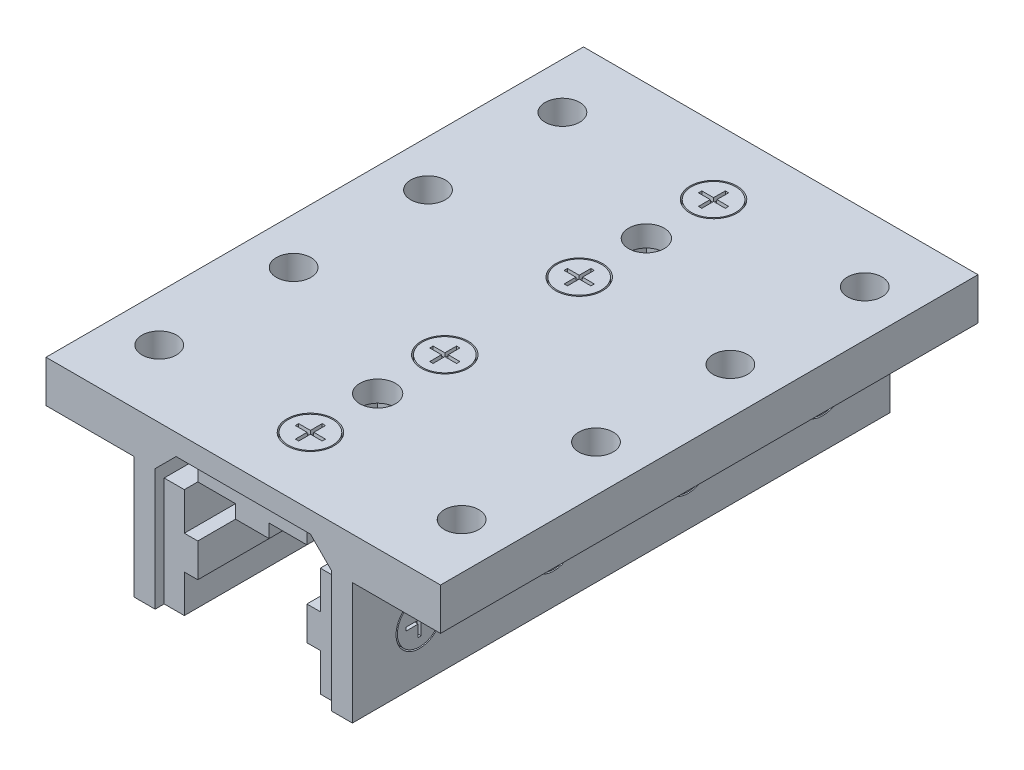
SolidWorks part; units mm, degrees
ref_plane "Front" through (0, 0, 0) normal (0, 0, 1) x (1, 0, 0)
ref_plane "Top" through (0, 0, 0) normal (0, 1, 0) x (1, 0, 0)
ref_plane "Right" through (0, 0, 0) normal (1, 0, 0) x (0, 0, -1)
sketch "Sketch1" plane through (0, 0, 0) normal (0, 0, 1) x (1, 0, 0)
  line L0 (-16.6624, 0) -> (-16.6624, 23.0124)
  line L1 (-20.6248, 30.9372) -> (20.6248, 30.9372)
  line L2 (-20.6248, 30.9372) -> (-20.6248, 0)
  line L3 (-20.6248, 0) -> (-16.6624, 0)
  line L4 (20.6248, 30.9372) -> (20.6248, 0)
  line L5 (-16.6624, 23.0124) -> (-12.7, 26.9748)
  line L6 (-12.7, 26.9748) -> (12.7, 26.9748)
  line L7 (12.7, 26.9748) -> (16.6624, 23.0124)
  line L8 (16.6624, 23.0124) -> (16.6624, 0)
  line L9 (16.6624, 0) -> (20.6248, 0)
  line L11 (-16.6624, 0) -> (16.6624, 0) construction
  dimension "D2" = 45
extrude "Boss-Extrude1" add sketch "Sketch1" along normal mid plane 50.8
sketch "Sketch2" plane through (0, 0, 0) normal (0, 0, 1) x (1, 0, 0)
  line L0 (-12.8524, 13.4874) -> (-12.8524, 20.6248)
  line L1 (-16.6624, 0) -> (-12.8524, 0)
  line L2 (-16.6624, 0) -> (-16.6624, 20.6248)
  line L3 (-16.6624, 20.6248) -> (-12.8524, 20.6248)
  line L4 (-12.8524, 0) -> (-12.8524, 7.1374)
  line L5 (-12.8524, 13.4874) -> (-10.3124, 13.4874)
  line L7 (-12.8524, 7.1374) -> (-10.3124, 7.1374)
  line L8 (-10.3124, 13.4874) -> (-10.3124, 7.1374)
  line L12 (-12.7, 26.9748) -> (12.7, 26.9748) construction
  line L13 (-10.3124, 26.9748) -> (10.3124, 26.9748)
  line L14 (-10.3124, 26.9748) -> (-10.3124, 23.1648)
  line L15 (-10.3124, 23.1648) -> (-3.175, 23.1648)
  line L16 (10.3124, 26.9748) -> (10.3124, 23.1648)
  line L17 (3.175, 23.1648) -> (10.3124, 23.1648)
  line L19 (-3.175, 23.1648) -> (-3.175, 20.6248)
  line L20 (-3.175, 20.6248) -> (3.175, 20.6248)
  line L21 (3.175, 23.1648) -> (3.175, 20.6248)
  point P14 (-10.3124, 10.3124)
  point P28 (0, 26.9748)
  dimension "Pad Wd" = 20.6248
  dimension "Pad Thick 1" = 6.35
  dimension "Pad Thick 2" = 3.81
  dimension "Pad Nose" = 6.35
extrude "Boss-Extrude2" add sketch "Sketch2" along normal mid plane 47.371 separate body
sketch "Sketch11" plane through (-10.3124, 0, 0) normal (1, 0, 0) x (0, 0, -1)
  line L0 (-23.6855, 13.4874) -> (23.6855, 13.4874) construction
  line L1 (-3.175, 13.4874) -> (3.175, 13.4874)
  line L2 (-3.175, 13.4874) -> (-3.175, 7.1374)
  line L3 (-3.175, 7.1374) -> (3.175, 7.1374)
  line L4 (3.175, 13.4874) -> (3.175, 7.1374)
  line L5 (-23.6855, 7.1374) -> (23.6855, 7.1374) construction
  point P8 (0, 13.4874)
extrude "Cut-Extrude5" cut sketch "Sketch11" against normal through all
sketch "Sketch12" plane through (0, 20.6248, 0) normal (0, -1, 0) x (1, 0, 0)
  line L0 (-3.175, 23.6855) -> (-3.175, -23.6855) construction
  line L1 (-3.175, 3.175) -> (3.175, 3.175)
  line L2 (-3.175, 3.175) -> (-3.175, -3.175)
  line L3 (-3.175, -3.175) -> (3.175, -3.175)
  line L4 (3.175, 3.175) -> (3.175, -3.175)
  line L5 (3.175, 23.6855) -> (3.175, -23.6855) construction
  point P8 (-3.175, 0)
extrude "Cut-Extrude6" cut sketch "Sketch12" against normal through all
mirror "Mirror1" about plane through (0, 0, 0) normal (1, 0, 0) of bodies 126 109
sketch "Sketch3" plane through (0, 30.9372, 0) normal (0, 1, 0) x (1, 0, 0)
  line L0 (0, -12.7) -> (0, 12.7) construction
  circle A0 centre (0, -12.7) radius 4.445
  circle A1 centre (0, -12.7) radius 4.191
extrude "Cut-Extrude1" cut sketch "Sketch3" against normal blind 1.9812
sketch "Sketch5" plane through (0, 30.9372, 0) normal (0, 1, 0) x (1, 0, 0)
  line L0 (0.3175, -12.3825) -> (2.54, -12.3825)
  line L1 (-0.3175, -10.16) -> (0.3175, -10.16)
  line L2 (-0.3175, -10.16) -> (-0.3175, -12.3825)
  line L3 (-0.3175, -15.24) -> (0.3175, -15.24)
  line L4 (0.3175, -10.16) -> (0.3175, -12.3825)
  line L5 (-2.54, -12.3825) -> (-0.3175, -12.3825)
  line L6 (-2.54, -12.3825) -> (-2.54, -13.0175)
  line L7 (-2.54, -13.0175) -> (-0.3175, -13.0175)
  line L8 (2.54, -12.3825) -> (2.54, -13.0175)
  line L9 (-0.3175, -13.0175) -> (-0.3175, -15.24)
  line L10 (0.3175, -13.0175) -> (0.3175, -15.24)
  line L11 (0.3175, -13.0175) -> (2.54, -13.0175)
  line L12 (-0.3175, -12.3825) -> (0.3175, -13.0175) construction
  dimension "D1" = 0.635
  dimension "D2" = 5.08
extrude "Cut-Extrude2" cut sketch "Sketch5" against normal blind 0.762 draft 5
sketch "Sketch13" plane through (20.6248, 0, 0) normal (1, 0, 0) x (0, 0, -1)
  circle A0 centre (-12.7, 10.3124) radius 4.445
  dimension "D1" = 8.89
extrude "Cut-Extrude-Thin1" cut sketch "Sketch13" against normal blind 1.9812 thin thin type one direction reverse wall 0.254
sketch "Sketch14" plane through (20.6248, 0, 0) normal (1, 0, 0) x (0, 0, -1)
  line L0 (-13.0175, 9.9949) -> (-13.0175, 7.7724)
  line L1 (-13.0175, 12.8524) -> (-12.3825, 12.8524)
  line L2 (-13.0175, 12.8524) -> (-13.0175, 10.6299)
  line L3 (-13.0175, 7.7724) -> (-12.3825, 7.7724)
  line L4 (-12.3825, 12.8524) -> (-12.3825, 10.6299)
  line L5 (-15.24, 10.6299) -> (-13.0175, 10.6299)
  line L6 (-15.24, 10.6299) -> (-15.24, 9.9949)
  line L7 (-15.24, 9.9949) -> (-13.0175, 9.9949)
  line L8 (-10.16, 10.6299) -> (-10.16, 9.9949)
  line L9 (-12.3825, 10.6299) -> (-10.16, 10.6299)
  line L10 (-12.3825, 9.9949) -> (-12.3825, 7.7724)
  line L11 (-12.3825, 9.9949) -> (-10.16, 9.9949)
  line L12 (-13.0175, 10.6299) -> (-12.3825, 9.9949) construction
  dimension "D1" = 0.635
  dimension "D2" = 5.08
extrude "Cut-Extrude7" cut sketch "Sketch14" against normal blind 0.762 draft 5
mirror "Mirror4" about plane through (0, 0, 0) normal (1, 0, 0) of "Cut-Extrude7", "Cut-Extrude-Thin1"
mirror "Mirror3" about plane through (0, 0, 0) normal (0, 0, 1) of "Mirror4", "Cut-Extrude-Thin1", "Cut-Extrude7", "Cut-Extrude1", "Cut-Extrude2"
sketch "Sketch9" plane through (0, 30.9372, 0) normal (0, 1, 0) x (1, 0, 0)
  circle A0 centre (0, 0) radius 3.3655
  dimension "Top Hole Dia" = 6.731
extrude "Cut-Extrude4" cut sketch "Sketch9" against normal through all
sketch "Sketch15" plane through (0, 0, 0) normal (1, 0, 0) x (0, 0, -1)
  circle A0 centre (0, 10.3124) radius 3.3655
  dimension "Side Wall Hole Dia" = 6.731
extrude "Cut-Extrude8" cut sketch "Sketch15" against normal through all and the other way through all
sketch "Sketch16" plane through (0, 0, 0) normal (0, 0, 1) x (1, 0, 0)
  line L1 (-37.2872, 30.9372) -> (-18.6436, 30.9372)
  line L2 (-37.2872, 30.9372) -> (-37.2872, 23.0124)
  line L3 (-37.2872, 23.0124) -> (-18.6436, 23.0124)
  line L4 (-18.6436, 30.9372) -> (-18.6436, 23.0124)
  line L5 (20.6248, 30.9372) -> (-20.6248, 30.9372) construction
  line L6 (18.6436, 30.9372) -> (37.2872, 30.9372)
  line L7 (18.6436, 30.9372) -> (18.6436, 23.0124)
  line L8 (18.6436, 23.0124) -> (37.2872, 23.0124)
  line L9 (37.2872, 30.9372) -> (37.2872, 23.0124)
  line L10 (-20.6248, 0) -> (-16.6624, 0) construction
  line L11 (16.6624, 0) -> (20.6248, 0) construction
  point P4 (-18.6436, 0)
  point P13 (18.6436, 0)
  dimension "Oall Wd" = 74.5744
  dimension "Top Flange Thickness" = 7.9248
extrude "Top Flange" add sketch "Sketch16" along normal up to surface (25.4 mm away) and the other way up to surface (25.4 mm away) up to face at (0, 16.1849, 25.4) other way up to face at (0, 16.1849, -25.4)
sketch "Sketch17" plane through (0, 30.9372, 0) normal (0, 1, 0) x (1, 0, 0)
  line L0 (-28.575, 12.7) -> (28.575, -12.7) construction
  line L1 (-28.575, 12.7) -> (28.575, 12.7) construction
  line L2 (-28.575, 12.7) -> (-28.575, -12.7) construction
  line L3 (-28.575, -12.7) -> (28.575, -12.7) construction
  line L4 (28.575, 12.7) -> (28.575, -12.7) construction
  line L5 (-18.6436, 12.7) -> (-20.6248, 12.7) construction
  circle A0 centre (28.575, 12.7) radius 3.2639
  circle A1 centre (28.575, -12.7) radius 3.2639
  circle A2 centre (-28.575, 12.7) radius 3.2639
  circle A3 centre (-28.575, -12.7) radius 3.2639
  dimension "Top Flange Hole Dia" = 6.5278
  dimension "Top Flange Hole Spacing" = 57.15
extrude "Top Flange Hole" cut sketch "Sketch17" against normal through all
mirror "Mirror7" about plane through (-20.6248, 0, -25.4) normal (0, 0, 1) of bodies 126 128 114
mirror "Mirror6" about plane through (-20.6248, 0, -25.4) normal (0, 0, 1) of bodies 135 134
other "Delete Hole Short" [suppressed]
other "Delete Hole Long" [suppressed]
pattern_linear "LPattern1" [suppressed] count 2 count 2 spacing 19.05 of bodies 136 128 138
sketch "Sketch19" [suppressed] plane through (0, 0, 0) normal (0, 0, 1) x (1, 0, 0)
  line L0 (-23.622, 47.625) -> (-14.478, 47.625) construction
  line L1 (-88.9, 47.625) -> (-23.622, 47.625)
  line L2 (-88.9, 47.625) -> (-88.9, 0)
  line L3 (-88.9, 0) -> (-23.622, 0)
  line L4 (-23.622, 47.625) -> (-23.622, 0)
  line L5 (14.478, 47.625) -> (-14.478, 47.625)
  line L6 (14.478, 47.625) -> (14.478, 0)
  line L7 (14.478, 0) -> (-14.478, 0)
  line L8 (-14.478, 47.625) -> (-14.478, 0)
  line L9 (-69.85, 0) -> (-63.5, 0) construction
  line L11 (14.478, 47.625) -> (23.622, 47.625) construction
  line L12 (23.622, 47.625) -> (88.9, 47.625)
  line L13 (23.622, 47.625) -> (23.622, 0)
  line L14 (23.622, 0) -> (88.9, 0)
  line L15 (88.9, 47.625) -> (88.9, 0)
  line L17 (-22.987, 31.75) -> (-15.113, 31.75) construction
  line L18 (15.113, 31.75) -> (22.987, 31.75) construction
  point P8 (-19.05, 47.625)
  point P9 (-19.05, 31.75)
  point P12 (19.05, 31.75)
  point P19 (19.05, 47.625)
  dimension "D1" = 9.144
extrude "Cut-Extrude12" [suppressed] cut sketch "Sketch19" against normal through all and the other way through all flip side to cut
sketch "Sketch20" [suppressed] plane through (0, 0, 0) normal (0, 0, 1) x (1, 0, 0)
  line L4 (14.478, 47.625) -> (-14.478, 47.625)
  line L5 (-14.478, 47.625) -> (-14.478, 0)
  line L6 (-14.478, 0) -> (14.478, 0)
  line L7 (14.478, 0) -> (14.478, 47.625)
  line L8 (88.9, 47.625) -> (-14.478, 47.625)
  line L9 (-14.478, 47.625) -> (-14.478, 0)
  line L10 (-14.478, 0) -> (88.9, 0)
  line L12 (-23.622, 47.625) -> (-88.9, 47.625)
  line L13 (-23.622, 0) -> (-23.622, 47.625)
  line L14 (-88.9, 0) -> (-23.622, 0)
  line L15 (-88.9, 47.625) -> (-88.9, 0)
  line L16 (-23.622, 47.625) -> (-88.9, 47.625)
  line L17 (-23.622, 0) -> (-23.622, 47.625)
  line L18 (-88.9, 0) -> (-23.622, 0)
  line L19 (-88.9, 47.625) -> (-88.9, 0)
  line L20 (88.9, 47.625) -> (23.622, 47.625)
  line L21 (23.622, 47.625) -> (23.622, 0)
  line L22 (23.622, 0) -> (88.9, 0)
  line L23 (88.9, 0) -> (88.9, 47.625)
  line L27 (88.9, 0) -> (88.9, 47.625)
  dimension "D1" = 0
  dimension "D2" = 0
  dimension "D3" = 0
extrude "Cut-Extrude14" [suppressed] cut sketch "Sketch20" against normal through all and the other way through all
sketch "Sketch21" [suppressed] plane through (0, 0, 0) normal (0, 0, 1) x (1, 0, 0)
  line L4 (14.478, 47.625) -> (-14.478, 47.625)
  line L5 (-14.478, 47.625) -> (-14.478, 0)
  line L6 (-14.478, 0) -> (14.478, 0)
  line L7 (14.478, 0) -> (14.478, 47.625)
  line L8 (14.478, 47.625) -> (-88.9, 47.625)
  line L10 (-88.9, 0) -> (14.478, 0)
  line L11 (14.478, 0) -> (14.478, 47.625)
  line L12 (-23.622, 47.625) -> (-88.9, 47.625)
  line L13 (-23.622, 0) -> (-23.622, 47.625)
  line L14 (-88.9, 0) -> (-23.622, 0)
  line L15 (-88.9, 47.625) -> (-88.9, 0)
  line L19 (-88.9, 47.625) -> (-88.9, 0)
  line L20 (88.9, 47.625) -> (23.622, 47.625)
  line L21 (23.622, 47.625) -> (23.622, 0)
  line L22 (23.622, 0) -> (88.9, 0)
  line L23 (88.9, 0) -> (88.9, 47.625)
  line L24 (88.9, 47.625) -> (23.622, 47.625)
  line L25 (23.622, 47.625) -> (23.622, 0)
  line L26 (23.622, 0) -> (88.9, 0)
  line L27 (88.9, 0) -> (88.9, 47.625)
  dimension "D1" = 0
  dimension "D2" = 0
  dimension "D3" = 0
extrude "Cut-Extrude15" [suppressed] cut sketch "Sketch21" against normal through all and the other way through all
sketch "Sketch22" [suppressed] plane through (0, 0, 38.1) normal (0, 0, 1) x (1, 0, 0)
  line L4 (-14.478, 41.275) -> (14.478, 41.275)
  line L5 (14.478, 41.275) -> (14.478, 47.625)
  line L6 (14.478, 47.625) -> (-14.478, 47.625)
  line L7 (14.478, 41.275) -> (14.478, 47.625)
  line L8 (-14.478, 41.275) -> (14.478, 41.275)
  line L9 (-14.478, 47.625) -> (-14.478, 41.275)
  line L10 (14.478, 47.625) -> (-14.478, 47.625)
  line L11 (-14.478, 47.625) -> (-14.478, 41.275)
  dimension "D1" = 0
extrude "Boss-Extrude4" [suppressed] add sketch "Sketch22" against normal through all
combine bodies "Combine1" [suppressed] operation type add bodies to combine 160 166 170 159 167
delete or keep bodies "Body-Delete1" [suppressed] type delete bodies bodies 128 138
pattern_linear "LPattern2" [suppressed] count 2 count 2 spacing 19.05 of bodies 169 128 135
sketch "Sketch23" [suppressed] plane through (0, 0, 0) normal (0, 0, 1) x (1, 0, 0)
  line L0 (-15.875, 20.6248) -> (-9.525, 20.6248) construction
  line L1 (-82.55, 47.625) -> (-17.272, 47.625)
  line L2 (-82.55, 47.625) -> (-82.55, 0)
  line L3 (-82.55, 0) -> (-17.272, 0)
  line L4 (-17.272, 47.625) -> (-17.272, 0)
  line L5 (82.55, 47.625) -> (17.272, 47.625)
  line L6 (82.55, 47.625) -> (82.55, 0)
  line L7 (82.55, 0) -> (17.272, 0)
  line L8 (17.272, 47.625) -> (17.272, 0)
  line L9 (-17.272, 47.625) -> (-8.128, 47.625) construction
  line L10 (-8.128, 47.625) -> (8.128, 47.625)
  line L11 (-8.128, 47.625) -> (-8.128, 0)
  line L12 (-8.128, 0) -> (8.128, 0)
  line L13 (8.128, 47.625) -> (8.128, 0)
  line L14 (8.128, 47.625) -> (17.272, 47.625) construction
  line L15 (-63.5, 0) -> (-57.15, 0) construction
  line L16 (9.525, 20.6248) -> (15.875, 20.6248) construction
  point P10 (-12.7, 47.625)
  point P11 (12.7, 47.625)
  point P17 (-12.7, 20.6248)
  point P18 (12.7, 20.6248)
  dimension "D1" = 9.144
extrude "Cut-Extrude16" [suppressed] cut sketch "Sketch23" against normal through all and the other way through all flip side to cut
sketch "Sketch24" [suppressed] plane through (0, 0, 0) normal (0, 0, 1) x (1, 0, 0)
  line L4 (8.128, 47.625) -> (-8.128, 47.625)
  line L5 (8.128, 0) -> (8.128, 47.625)
  line L6 (-8.128, 0) -> (8.128, 0)
  line L7 (-8.128, 47.625) -> (-8.128, 0)
  line L8 (82.55, 47.625) -> (-8.128, 47.625)
  line L10 (-8.128, 0) -> (82.55, 0)
  line L11 (-8.128, 47.625) -> (-8.128, 0)
  line L12 (82.55, 47.625) -> (17.272, 47.625)
  line L13 (17.272, 47.625) -> (17.272, 0)
  line L14 (17.272, 0) -> (82.55, 0)
  line L15 (82.55, 0) -> (82.55, 47.625)
  line L19 (82.55, 0) -> (82.55, 47.625)
  line L20 (-17.272, 47.625) -> (-82.55, 47.625)
  line L21 (-17.272, 0) -> (-17.272, 47.625)
  line L22 (-82.55, 0) -> (-17.272, 0)
  line L23 (-82.55, 47.625) -> (-82.55, 0)
  line L24 (-17.272, 47.625) -> (-82.55, 47.625)
  line L25 (-17.272, 0) -> (-17.272, 47.625)
  line L26 (-82.55, 0) -> (-17.272, 0)
  line L27 (-82.55, 47.625) -> (-82.55, 0)
  dimension "D1" = 0
  dimension "D2" = 0
  dimension "D3" = 0
extrude "Cut-Extrude17" [suppressed] cut sketch "Sketch24" against normal through all and the other way through all
sketch "Sketch25" [suppressed] plane through (0, 0, 0) normal (0, 0, 1) x (1, 0, 0)
  line L4 (8.128, 47.625) -> (-8.128, 47.625)
  line L5 (8.128, 0) -> (8.128, 47.625)
  line L6 (-8.128, 0) -> (8.128, 0)
  line L7 (-8.128, 47.625) -> (-8.128, 0)
  line L8 (8.128, 47.625) -> (-82.55, 47.625)
  line L9 (8.128, 0) -> (8.128, 47.625)
  line L10 (-82.55, 0) -> (8.128, 0)
  line L12 (82.55, 47.625) -> (17.272, 47.625)
  line L13 (17.272, 47.625) -> (17.272, 0)
  line L14 (17.272, 0) -> (82.55, 0)
  line L15 (82.55, 0) -> (82.55, 47.625)
  line L16 (82.55, 47.625) -> (17.272, 47.625)
  line L17 (17.272, 47.625) -> (17.272, 0)
  line L18 (17.272, 0) -> (82.55, 0)
  line L19 (82.55, 0) -> (82.55, 47.625)
  line L20 (-17.272, 47.625) -> (-82.55, 47.625)
  line L21 (-17.272, 0) -> (-17.272, 47.625)
  line L22 (-82.55, 0) -> (-17.272, 0)
  line L23 (-82.55, 47.625) -> (-82.55, 0)
  line L27 (-82.55, 47.625) -> (-82.55, 0)
  dimension "D1" = 0
  dimension "D2" = 0
  dimension "D3" = 0
extrude "Cut-Extrude18" [suppressed] cut sketch "Sketch25" against normal through all and the other way through all
sketch "Sketch26" [suppressed] plane through (0, 0, 38.1) normal (0, 0, 1) x (1, 0, 0)
  line L4 (8.128, 47.625) -> (-8.128, 47.625)
  line L5 (-8.128, 47.625) -> (-8.128, 41.275)
  line L6 (-8.128, 41.275) -> (8.128, 41.275)
  line L7 (8.128, 41.275) -> (8.128, 47.625)
  line L8 (8.128, 47.625) -> (-8.128, 47.625)
  line L9 (-8.128, 47.625) -> (-8.128, 41.275)
  line L10 (-8.128, 41.275) -> (8.128, 41.275)
  line L11 (8.128, 41.275) -> (8.128, 47.625)
  dimension "D1" = 0
extrude "Boss-Extrude5" [suppressed] add sketch "Sketch26" against normal through all
combine bodies "Combine2" [suppressed] operation type add bodies to combine 181 179 184 180 182
delete or keep bodies "Body-Delete4" [suppressed] type delete bodies bodies 128
equation "\"D1@Cut-Extrude1\" = \"Top Thick@Sketch1\" * .5"
equation "\"D1@Sketch13\" = \"Screw Head Dia@Sketch3\""
equation "\"D1@Cut-Extrude-Thin1\" = \"Leg Thick@Sketch1\" * .5"
equation "\"D5@Cut-Extrude-Thin1\" = \"D1@Sketch3\""
equation "\"D1@Cut-Extrude7\" = \"D1@Cut-Extrude2\""
equation "\"D1@Sketch14\" = \"D1@Sketch5\""
equation "\"D2@Sketch14\" = \"D2@Sketch5\""
equation "\"D3@Cut-Extrude7\" = \"D3@Cut-Extrude2\""
equation "\"D4@LPattern1\" = \"Double Wd Offset@LPattern1\""
equation "\"D4@LPattern2\" = \"Double Wd Offset@LPattern2\""
